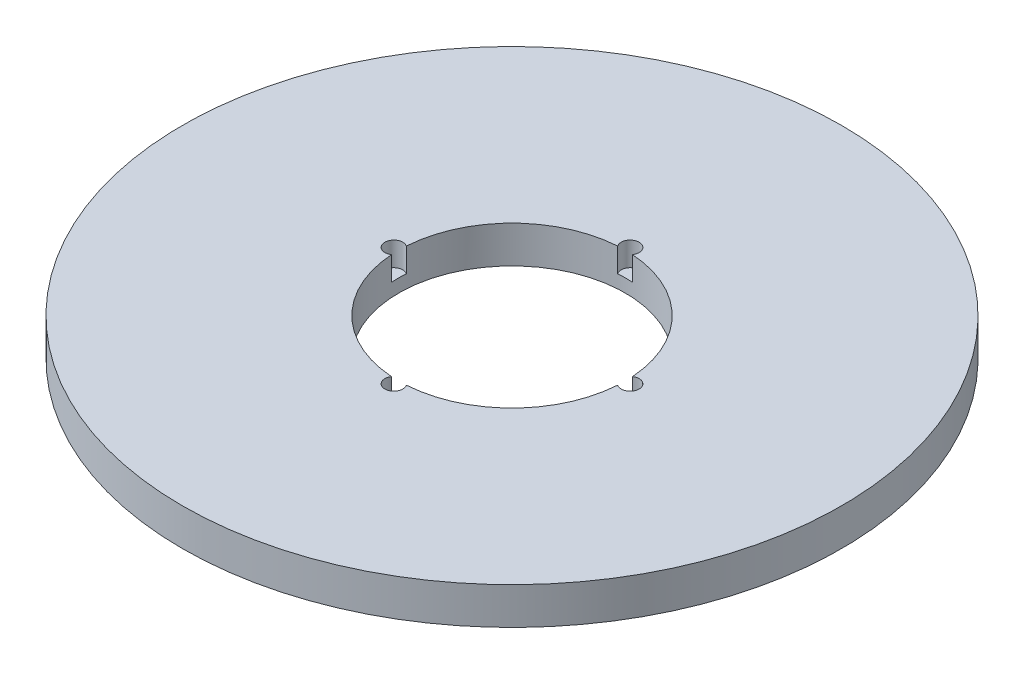
SolidWorks part; units mm, degrees
ref_plane "Front Plane" through (0, 0, 0) normal (0, 0, 1) x (1, 0, 0)
ref_plane "Top Plane" through (0, 0, 0) normal (0, 1, 0) x (1, 0, 0)
ref_plane "Right Plane" through (0, 0, 0) normal (1, 0, 0) x (0, 0, -1)
sketch "Sketch1" plane through (0, 0, 0) normal (0, 1, 0) x (1, 0, 0)
  circle A0 centre (0, 0) radius 80
  dimension "FLANGE_OD" = 160
extrude "Boss-Extrude1" add sketch "Sketch1" along normal blind 9
sketch "Sketch2" plane through (0, 0, 0) normal (0, 1, 0) x (1, 0, 0)
  circle A0 centre (0, 0) radius 27.5
  dimension "BORE_D" = 55
extrude "Cut-Extrude1" cut sketch "Sketch2" along normal through all
sketch "Sketch3" plane through (0, 9, 0) normal (0, 1, 0) x (1, 0, 0)
  circle A0 centre (0, 0) radius 28.6873 construction
  circle A1 centre (-28.6873, 0) radius 2.1809
  dimension "BOLT_D" = 4.3617
  dimension "BOLT_PCD" = 57.3745
extrude "Cut-Extrude2" cut sketch "Sketch3" against normal blind 5.8181
pattern_circular "CirPattern1" count 4 over 360 about axis through (0, 0, 0) along (0, 1, 0) of "Cut-Extrude2"
